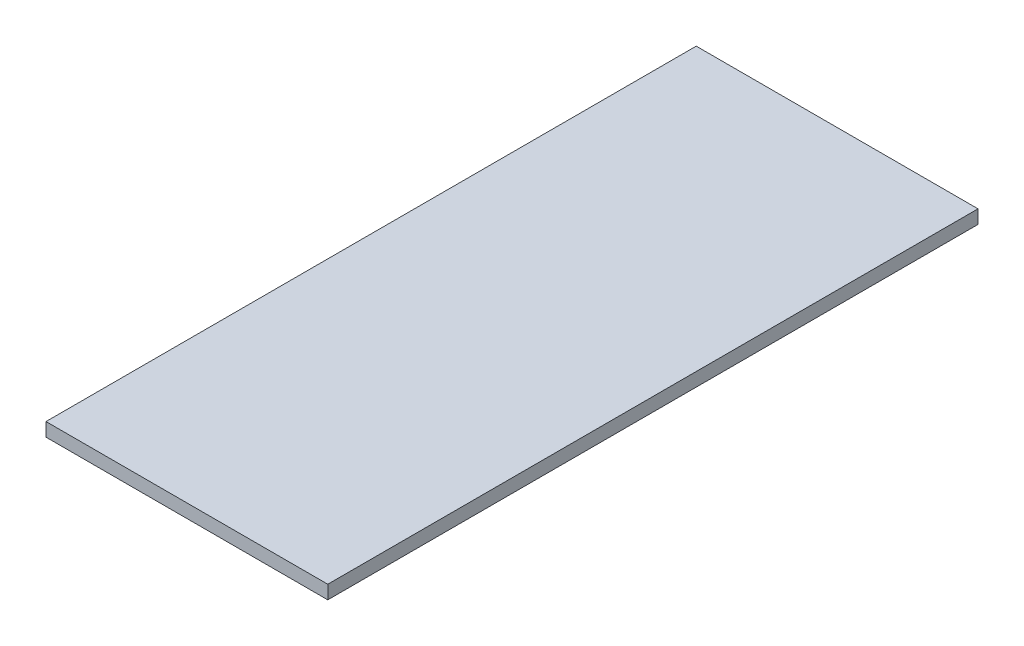
SolidWorks part; units mm, degrees
ref_plane "Front Plane" through (0, 0, 0) normal (0, 0, 1) x (1, 0, 0)
ref_plane "Top Plane" through (0, 0, 0) normal (0, 1, 0) x (1, 0, 0)
ref_plane "Right Plane" through (0, 0, 0) normal (1, 0, 0) x (0, 0, -1)
sketch "Sketch1" plane through (0, 0, 0) normal (0, 1, 0) x (1, 0, 0)
  line L1 (0, 0) -> (66.04, 0)
  line L2 (0, 0) -> (0, 152.4)
  line L3 (0, 152.4) -> (66.04, 152.4)
  line L4 (66.04, 0) -> (66.04, 152.4)
  dimension "D1" = 66.04
  dimension "D2" = 152.4
extrude "Boss-Extrude1" add sketch "Sketch1" along normal blind 3.175
